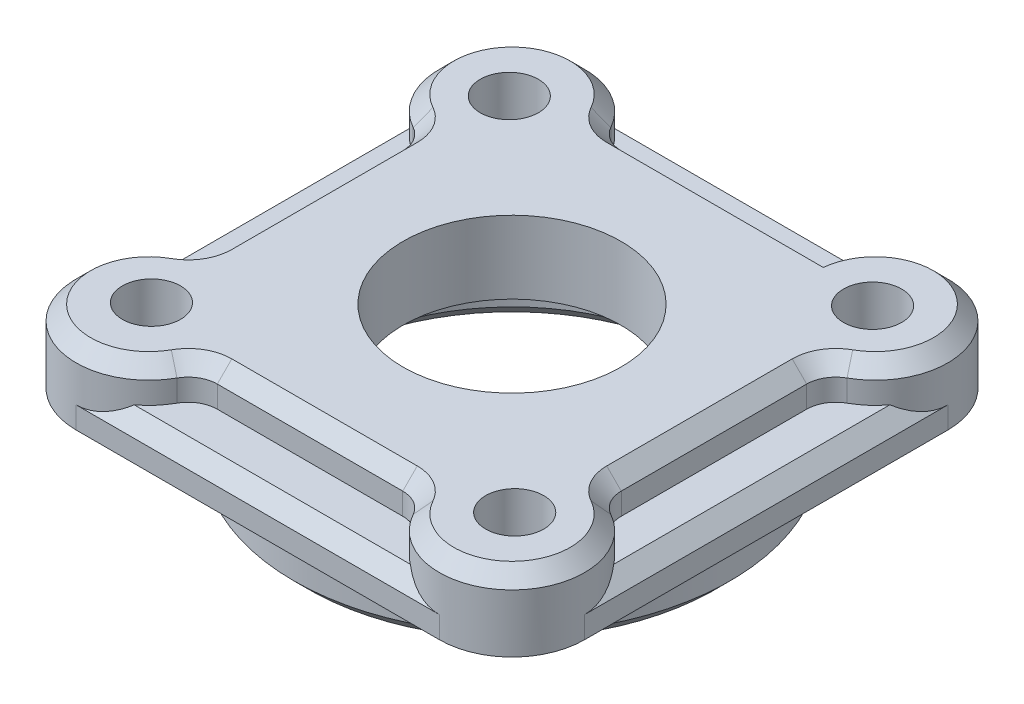
SolidWorks part; units mm, degrees
material "6061 Alloy"
ref_plane "Front Plane" through (0, 0, 0) normal (0, 0, 1) x (1, 0, 0)
ref_plane "Top Plane" through (0, 0, 0) normal (0, 1, 0) x (1, 0, 0)
ref_plane "Right Plane" through (0, 0, 0) normal (1, 0, 0) x (0, 0, -1)
sketch "Sketch1" plane through (0, 0, 0) normal (0, 1, 0) x (1, 0, 0)
  line L0 (-26.8003, 0) -> (39.2381, 0) construction
  line L1 (0, -23.9826) -> (0, 26.2978) construction
  line L3 (-15.875, -22.225) -> (15.875, -22.225)
  line L4 (-22.225, -15.875) -> (-22.225, 15.875)
  line L5 (-15.875, 22.225) -> (15.875, 22.225)
  line L6 (22.225, -15.875) -> (22.225, 15.875)
  arc A0 (-15.875, 22.225) -> (-22.225, 15.875) centre (-15.875, 15.875) ccw
  arc A1 (15.875, 22.225) -> (22.225, 15.875) centre (15.875, 15.875) cw
  arc A2 (-15.875, -22.225) -> (-22.225, -15.875) centre (-15.875, -15.875) cw
  arc A3 (15.875, -22.225) -> (22.225, -15.875) centre (15.875, -15.875) ccw
  point P5 (0, 0)
  point P6 (22.225, 0)
  point P7 (0, -22.225)
  dimension "D1" = 44.45
  dimension "D3" = 12.7
  dimension "D2" = 44.45
extrude "Boss-Extrude1" add sketch "Sketch1" along normal blind 3.175
sketch "Sketch2" plane through (0, 3.175, 0) normal (0, 1, 0) x (1, 0, 0)
  line L0 (0, -23.9826) -> (0, 26.2978) construction
  line L1 (-26.8003, 0) -> (39.2381, 0) construction
  line L2 (0, -23.9826) -> (0, 26.2978) construction
  line L3 (-26.8003, 0) -> (39.2381, 0) construction
  line L4 (-8.1045, 17.6536) -> (9.7792, 17.6536)
  line L5 (17.653, 8.1041) -> (17.653, -8.1041)
  line L6 (-8.1045, -17.6536) -> (8.1045, -17.6536)
  line L7 (-17.653, 8.1041) -> (-17.653, -8.1041)
  arc A0 (-15.875, 22.225) -> (-22.225, 15.875) centre (-15.875, 15.875) ccw construction
  arc A1 (-15.875, 22.225) -> (-22.225, 15.875) centre (-15.875, 15.875) ccw
  arc A2 (-10.3246, 18.9597) -> (-18.9593, 10.3244) centre (-15.875, 15.875) ccw
  arc A3 (9.7792, 17.6536) -> (18.9593, 10.3244) centre (15.875, 15.875) cw
  arc A4 (10.3246, -18.9597) -> (18.9593, -10.3244) centre (15.875, -15.875) ccw
  arc A5 (-10.3246, -18.9597) -> (-18.9593, -10.3244) centre (-15.875, -15.875) cw
  arc A6 (18.9593, 10.3244) -> (17.653, 8.1041) centre (20.193, 8.1041) ccw
  arc A7 (17.653, -8.1041) -> (18.9593, -10.3244) centre (20.193, -8.1041) ccw
  arc A8 (10.3246, -18.9597) -> (8.1045, -17.6536) centre (8.1045, -20.1936) ccw
  arc A9 (-8.1045, -17.6536) -> (-10.3246, -18.9597) centre (-8.1045, -20.1936) ccw
  arc A10 (-18.9593, -10.3244) -> (-17.653, -8.1041) centre (-20.193, -8.1041) ccw
  arc A11 (-17.653, 8.1041) -> (-18.9593, 10.3244) centre (-20.193, 8.1041) ccw
  arc A12 (-10.3246, 18.9597) -> (-8.1045, 17.6536) centre (-8.1045, 20.1936) ccw
  point P11 (17.653, 9.779)
  point P23 (17.653, -9.779)
  point P26 (9.7792, -17.6536)
  point P29 (-9.7792, -17.6536)
  point P32 (-17.653, -9.779)
  point P35 (-17.653, 9.779)
  point P38 (-9.7792, 17.6536)
  arc M3 (-15.875, 22.225) -> (-22.225, 15.875) centre (-15.875, 15.875) ccw
  arc M5 (-22.225, -15.875) -> (-15.875, -22.225) centre (-15.875, -15.875) ccw
  arc M7 (15.875, -22.225) -> (22.225, -15.875) centre (15.875, -15.875) ccw
  arc M9 (22.225, 15.875) -> (15.875, 22.225) centre (15.875, 15.875) ccw
  dimension "D3" = 2.54
  dimension "D1" = 17.6536
  dimension "D2" = 17.653
extrude "Boss-Extrude2" add sketch "Sketch2" along normal blind 3.175 contours A12 A2 A11 L7 A10 A5 A9 L6 A8 A4 A7 L5 A6 A3 L4 M3 M5 M7 M9 region at (-0.0028, 3.175, 0.0052)
sketch "Sketch3" plane through (0, 0, 0) normal (0, -1, 0) x (1, 0, 0)
  circle A0 centre (0, 0) radius 15.875
  circle A1 centre (0, 0) radius 19.05
  dimension "D1" = 31.75
  dimension "D2" = 38.1
extrude "Boss-Extrude3" add sketch "Sketch3" along normal blind 6.35
sketch "Sketch4" plane through (0, 6.35, 0) normal (0, 1, 0) x (1, 0, 0)
  line L0 (0, 0) -> (0, 23.4217) construction
  line L1 (0, 0) -> (24.4366, 0) construction
  circle A0 centre (-15.875, 15.6394) radius 2.54
  circle A2 centre (15.875, 15.6394) radius 2.54
  circle A3 centre (-15.875, -15.6394) radius 2.54
  circle A4 centre (15.875, -15.6394) radius 2.54
  dimension "D1" = 5.08
  dimension "D2" = 15.6394
extrude "Cut-Extrude1" cut sketch "Sketch4" against normal through all
chamfer "Chamfer1" distance 1.27 angle 45 21 edges at (0, -6.35, -15.875) (0, -6.35, -19.05) (19.8369, 6.35, -20.8374) (18.0038, 6.35, -9.3921) (17.653, 6.35, 0) (18.0038, 6.35, 9.3921) (20.3653, 6.35, 20.3649) (9.3924, 6.35, 18.0044) (0.8374, 6.35, -17.6536) (0, 6.35, 17.6536) (-9.3924, 6.35, -18.0044) (-9.3924, 6.35, 18.0044) (-20.3653, 6.35, -20.3649) (-20.3653, 6.35, 20.3649) (-18.0038, 6.35, -9.3921) (-18.0038, 6.35, 9.3921) (-17.653, 6.35, 0)
sketch "Sketch5" plane through (0, 6.35, 0) normal (0, 1, 0) x (1, 0, 0)
  circle A0 centre (0, 0) radius 9.525
  dimension "D1" = 19.05
extrude "Cut-Extrude2" cut sketch "Sketch5" against normal through all
